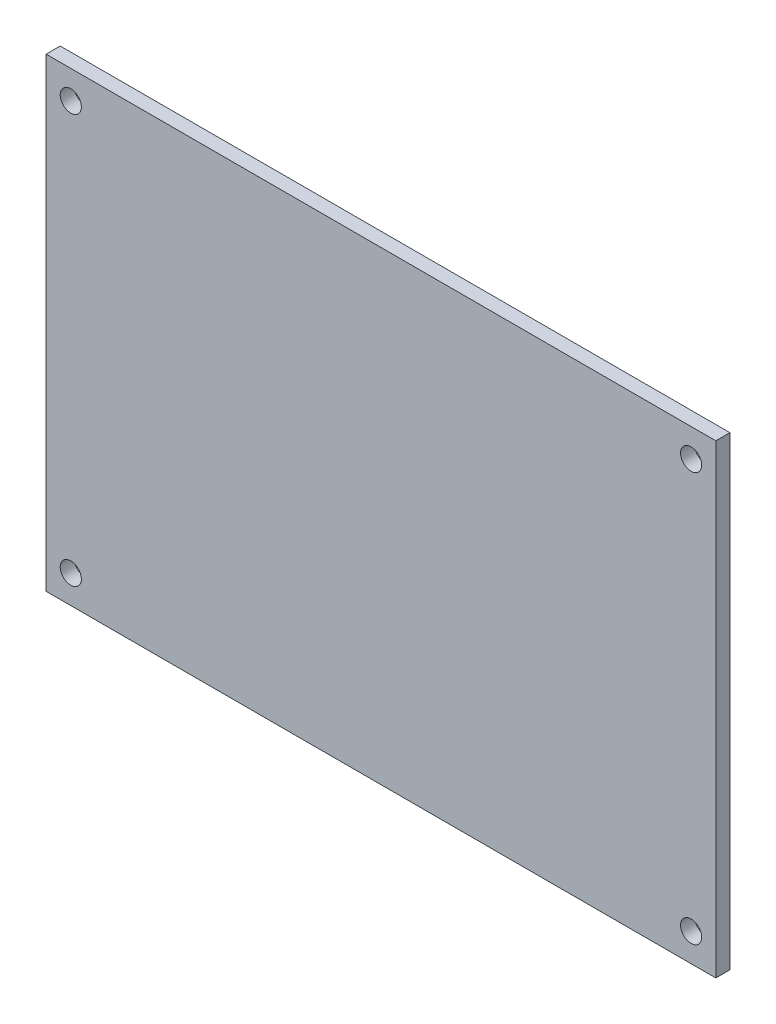
SolidWorks part; units mm, degrees
ref_plane "Front Plane" through (0, 0, 0) normal (0, 0, 1) x (1, 0, 0)
ref_plane "Top Plane" through (0, 0, 0) normal (0, 1, 0) x (1, 0, 0)
ref_plane "Right Plane" through (0, 0, 0) normal (1, 0, 0) x (0, 0, -1)
sketch "Sketch1" plane through (0, 0, 0) normal (0, 0, 1) x (1, 0, 0)
  line L1 (-95, 66) -> (0, 66)
  line L2 (-95, 66) -> (-95, 0)
  line L3 (-95, 0) -> (0, 0)
  line L4 (0, 66) -> (0, 0)
  dimension "D1" = 95
  dimension "D2" = 66
extrude "Boss-Extrude1" add sketch "Sketch1" along normal blind 2
sketch "Sketch2" plane through (0, 0, 2) normal (0, 0, 1) x (1, 0, 0)
  line L0 (0, 66) -> (-95, 66) construction
  line L1 (-3.5, 4) -> (-91.5, 4) construction
  line L2 (-3.5, 4) -> (-3.5, 62) construction
  line L3 (-3.5, 62) -> (-91.5, 62) construction
  line L4 (-91.5, 4) -> (-91.5, 62) construction
  line L5 (-3.5, 4) -> (-91.5, 62) construction
  line L6 (-3.5, 62) -> (-91.5, 4) construction
  line L7 (-95, 66) -> (-95, 0) construction
  circle A1 centre (-91.5, 62) radius 1.5
  circle A2 centre (-3.5, 62) radius 1.5
  circle A3 centre (-3.5, 4) radius 1.5
  circle A4 centre (-91.5, 4) radius 1.5
  point P0 (-47.5, 33)
  point P7 (-47.5, 66)
  point P10 (-95, 33)
  point P16 (0, 0)
  dimension "D1" = 3
  dimension "D2" = 88
  dimension "D3" = 58
extrude "Cut-Extrude1" cut sketch "Sketch2" against normal blind 2
